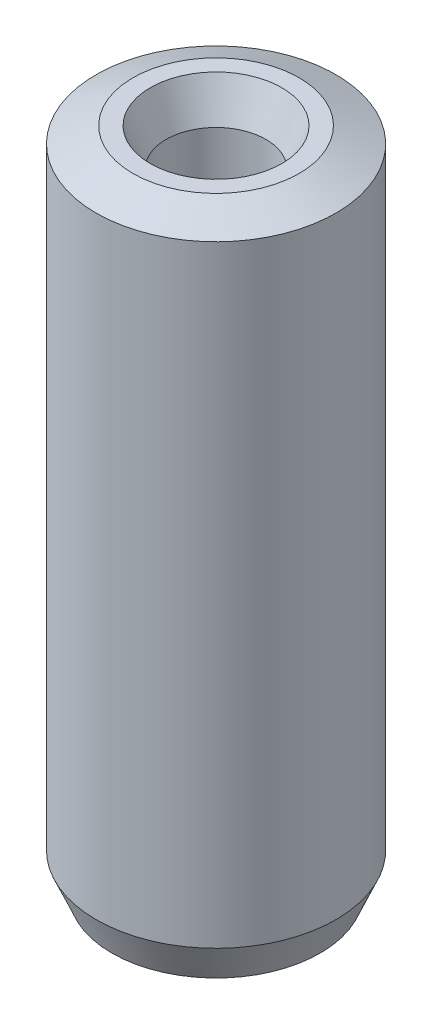
SolidWorks part; units mm, degrees
ref_plane "Front Plane" through (0, 0, 0) normal (0, 0, 1) x (1, 0, 0)
ref_plane "Top Plane" through (0, 0, 0) normal (0, 1, 0) x (1, 0, 0)
ref_plane "Right Plane" through (0, 0, 0) normal (1, 0, 0) x (0, 0, -1)
sketch "Sketch1" plane through (0, 0, 0) normal (0, 1, 0) x (1, 0, 0)
  circle A0 centre (0, 0) radius 5
  dimension "SLEEVE_OD" = 10
extrude "Boss-Extrude1" add sketch "Sketch1" along normal blind 27.7065
sketch "Sketch2" plane through (0, 0, 0) normal (0, 1, 0) x (1, 0, 0)
  circle A0 centre (0, 0) radius 2.0836
  dimension "BORE_D" = 4.1671
extrude "Cut-Extrude1" cut sketch "Sketch2" along normal through all
chamfer "Chamfer1" distance 0.6581 angle 66.842 4 edges at (0, 27.7065, 2.0836) (0, 0, 2.0836) (0, 0, 5) (0, 27.7065, 5) first distance on face at (0, 27.7065, 2.0836) first distance on face at (0, 0, 2.0836) first distance on face at (0, 27.7065, 5)
